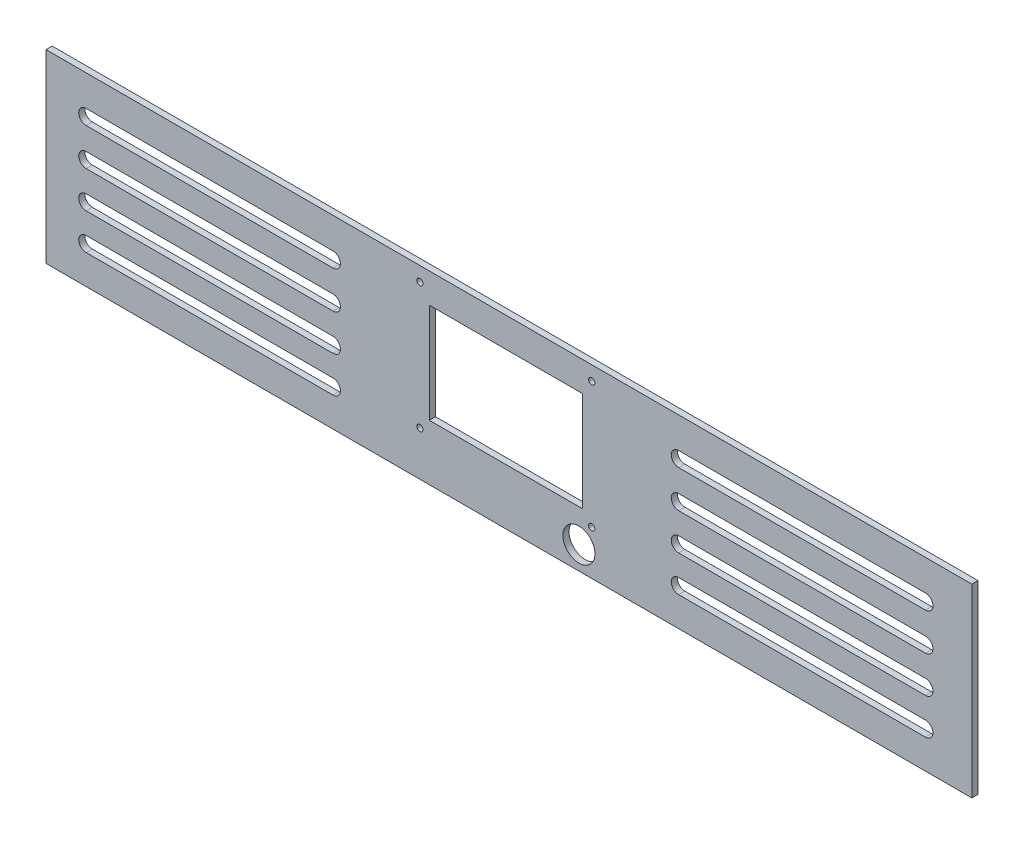
SolidWorks part; units mm, degrees
ref_plane "Front Plane" through (0, 0, 0) normal (0, 0, 1) x (1, 0, 0)
ref_plane "Top Plane" through (0, 0, 0) normal (0, 1, 0) x (1, 0, 0)
ref_plane "Right Plane" through (0, 0, 0) normal (1, 0, 0) x (0, 0, -1)
sketch "Sketch1" plane through (0, 0, 0) normal (0, 0, 1) x (1, 0, 0)
  line L1 (-236.5375, -47.625) -> (236.5375, -47.625)
  line L2 (-236.5375, -47.625) -> (-236.5375, 47.625)
  line L3 (-236.5375, 47.625) -> (236.5375, 47.625)
  line L4 (236.5375, -47.625) -> (236.5375, 47.625)
  line L5 (-236.5375, -47.625) -> (236.5375, 47.625) construction
  line L6 (-236.5375, 47.625) -> (236.5375, -47.625) construction
  point P0 (0, 0)
  dimension "D1" = 473.075
  dimension "D2" = 95.25
extrude "Boss-Extrude1" add sketch "Sketch1" along normal blind 3.175
sketch "Sketch3" plane through (0, 0, 3.175) normal (0, 0, 1) x (1, 0, 0)
  line L0 (0, -47.625) -> (0, -19.05)
  line L1 (-236.5375, -47.625) -> (236.5375, -47.625) construction
  line L3 (-39.37, -18.923) -> (39.37, -18.923)
  line L4 (-39.37, -18.923) -> (-39.37, 32.385)
  line L5 (-39.37, 32.385) -> (39.37, 32.385)
  line L6 (39.37, -18.923) -> (39.37, 32.385)
  dimension "D1" = 28.575
  dimension "D2" = 78.74
  dimension "D3" = 39.37
  dimension "D4" = 51.308
  dimension "D5" = 28.702
extrude "Cut-Extrude2" cut sketch "Sketch3" against normal through all contours L3 L6 L5 L4 region at (0, 6.731, 3.175)
sketch "Sketch4" plane through (0, 0, 3.175) normal (0, 0, 1) x (1, 0, 0)
  line L0 (-236.5375, -47.625) -> (236.5375, -47.625) construction
  line L1 (39.37, -18.923) -> (39.37, 32.385) construction
  circle A0 centre (37.592, -35.814) radius 8.255
  dimension "D1" = 16.51
  dimension "D2" = 11.811
  dimension "D3" = 1.778
extrude "Cut-Extrude3" cut sketch "Sketch4" against normal through all
sketch "Sketch5" plane through (0, 0, 3.175) normal (0, 0, 1) x (1, 0, 0)
  line L0 (39.37, -18.923) -> (39.37, 32.385) construction
  line L1 (-39.37, 32.385) -> (39.37, 32.385) construction
  line L2 (0, 0) -> (0, 11.1381)
  line L3 (0, 0) -> (6.9433, 0)
  circle A0 centre (44.196, 40.259) radius 1.5875
  circle A1 centre (44.196, -24.765) radius 1.5875
  circle A2 centre (-44.196, -24.765) radius 1.5875
  circle A3 centre (-44.196, 40.259) radius 1.5875
  dimension "D1" = 3.175
  dimension "D3" = 7.874
  dimension "D4" = 65.024
  dimension "D5" = 0
  dimension "D2" = 4.826
extrude "Cut-Extrude4" cut sketch "Sketch5" against normal through all contours A3 | A0 | A2 | A1 region at (44.196, 40.259, 3.175) region at (44.196, -24.765, 3.175) region at (-44.196, -24.765, 3.175) region at (-44.196, 40.259, 3.175)
sketch "Sketch6" plane through (0, 0, 0) normal (0, 0, -1) x (-1, 0, 0)
  line L0 (236.5375, -47.625) -> (-236.5375, -47.625) construction
  line L1 (236.5375, 47.625) -> (233.3625, 47.625)
  line L2 (236.5375, 47.625) -> (236.5375, -47.625)
  line L3 (236.5375, -47.625) -> (233.3625, -47.625)
  line L4 (233.3625, 47.625) -> (233.3625, -47.625)
  dimension "D1" = 3.175
extrude "Boss-Extrude2" add sketch "Sketch6" along normal blind 371.948
sketch "Sketch7" plane through (-236.5375, 0, 0) normal (-1, 0, 0) x (0, 0, 1)
  line L0 (3.175, 47.625) -> (-371.948, 47.625) construction
  line L1 (-333.848, 28.575) -> (-283.048, 28.575)
  line L2 (-333.848, 28.575) -> (-333.848, -44.45)
  line L3 (-333.848, -44.45) -> (-283.048, -44.45)
  line L4 (-283.048, 28.575) -> (-283.048, -44.45)
  line L5 (-371.948, -47.625) -> (-371.948, 47.625) construction
  line L6 (3.175, -47.625) -> (-371.948, -47.625) construction
  circle A0 centre (-248.25, -28.575) radius 3.81
  dimension "D5" = 123.698
  dimension "D6" = 19.05
  dimension "D1" = 19.05
  dimension "D2" = 50.8
  dimension "D3" = 38.1
  dimension "D4" = 3.175
extrude "Cut-Extrude5" cut sketch "Sketch7" against normal blind 381
sketch "Sketch8" plane through (0, 0, 3.175) normal (0, 0, 1) x (1, 0, 0)
  line L0 (88.9, 27.94) -> (215.9, 27.94) construction
  line L1 (88.9, 31.75) -> (215.9, 31.75)
  line L2 (88.9, 24.13) -> (215.9, 24.13)
  line L3 (88.9, 8.7536) -> (215.9, 8.7536) construction
  line L4 (88.9, 12.5636) -> (215.9, 12.5636)
  line L5 (88.9, 4.9436) -> (215.9, 4.9436)
  line L6 (88.9, -10.0663) -> (215.9, -10.0663) construction
  line L7 (88.9, -6.2563) -> (215.9, -6.2563)
  line L8 (88.9, -13.8763) -> (215.9, -13.8763)
  line L9 (88.9, -28.656) -> (215.9, -28.656) construction
  line L10 (88.9, -24.846) -> (215.9, -24.846)
  line L11 (88.9, -32.466) -> (215.9, -32.466)
  line L15 (-88.9, -28.656) -> (-215.9, -28.656) construction
  line L18 (-88.9, -24.846) -> (-215.9, -24.846)
  line L21 (-88.9, -32.466) -> (-215.9, -32.466)
  line L24 (-88.9, -10.0663) -> (-215.9, -10.0663) construction
  line L27 (-88.9, -6.2563) -> (-215.9, -6.2563)
  line L28 (-88.9, -13.8763) -> (-215.9, -13.8763)
  line L29 (-88.9, 8.7536) -> (-215.9, 8.7536) construction
  line L30 (-88.9, 12.5636) -> (-215.9, 12.5636)
  line L31 (-88.9, 4.9436) -> (-215.9, 4.9436)
  line L32 (-88.9, 27.94) -> (-215.9, 27.94) construction
  line L33 (-88.9, 31.75) -> (-215.9, 31.75)
  line L34 (-88.9, 24.13) -> (-215.9, 24.13)
  arc A0 (88.9, 31.75) -> (88.9, 24.13) centre (88.9, 27.94) ccw
  arc A1 (215.9, 24.13) -> (215.9, 31.75) centre (215.9, 27.94) ccw
  arc A2 (88.9, 12.5636) -> (88.9, 4.9436) centre (88.9, 8.7536) ccw
  arc A3 (215.9, 4.9436) -> (215.9, 12.5636) centre (215.9, 8.7536) ccw
  arc A4 (88.9, -6.2563) -> (88.9, -13.8763) centre (88.9, -10.0663) ccw
  arc A5 (215.9, -13.8763) -> (215.9, -6.2563) centre (215.9, -10.0663) ccw
  arc A6 (88.9, -24.846) -> (88.9, -32.466) centre (88.9, -28.656) ccw
  arc A7 (215.9, -32.466) -> (215.9, -24.846) centre (215.9, -28.656) ccw
  arc A16 (-88.9, -24.846) -> (-88.9, -32.466) centre (-88.9, -28.656) cw
  arc A17 (-215.9, -32.466) -> (-215.9, -24.846) centre (-215.9, -28.656) cw
  arc A18 (-88.9, -6.2563) -> (-88.9, -13.8763) centre (-88.9, -10.0663) cw
  arc A19 (-215.9, -13.8763) -> (-215.9, -6.2563) centre (-215.9, -10.0663) cw
  arc A20 (-88.9, 12.5636) -> (-88.9, 4.9436) centre (-88.9, 8.7536) cw
  arc A21 (-215.9, 4.9436) -> (-215.9, 12.5636) centre (-215.9, 8.7536) cw
  arc A22 (-88.9, 31.75) -> (-88.9, 24.13) centre (-88.9, 27.94) cw
  arc A23 (-215.9, 24.13) -> (-215.9, 31.75) centre (-215.9, 27.94) cw
  point P2 (152.4, 27.94)
  point P7 (152.4, 8.7536)
  point P16 (152.4, -10.0663)
  point P21 (152.4, -28.656)
  point P32 (-152.4, -28.656)
  point P39 (-152.4, -10.0663)
  point P46 (-152.4, 8.7536)
  point P53 (-152.4, 27.94)
extrude "Cut-Extrude6" cut sketch "Sketch8" against normal blind 381 contours L11 A7 L10 A6 | L8 A5 L7 A4 | L5 A3 L4 A2 | L2 A1 L1 A0 | L2 A1 L1 A0 | L33 A23 L34 A22 | L30 A21 L31 A20 | L27 A19 L28 A18 | L18 A17 L21 A16 region at (152.4, 27.94, 3.175) region at (152.4, 8.7536, 3.175) region at (152.4, -10.0663, 3.175) region at (152.4, -28.656, 3.175)
sketch "Sketch12" plane through (-233.3625, 0, 0) normal (1, 0, 0) x (0, 0, -1)
  line L1 (0, 47.625) -> (371.948, 47.625)
  line L2 (0, 47.625) -> (0, -47.625)
  line L3 (0, -47.625) -> (371.948, -47.625)
  line L4 (371.948, 47.625) -> (371.948, -47.625)
extrude "Cut-Extrude7" cut sketch "Sketch12" against normal blind 54.356
sketch "Sketch13" plane through (236.5375, 0, 0) normal (1, 0, 0) x (0, 0, -1)
  line L1 (0, 47.625) -> (-3.175, 47.625)
  line L2 (0, 47.625) -> (0, -47.625)
  line L3 (0, -47.625) -> (-3.175, -47.625)
  line L4 (-3.175, 47.625) -> (-3.175, -47.625)
extrude "Boss-Extrude3" add sketch "Sketch13" along normal blind 3.175
